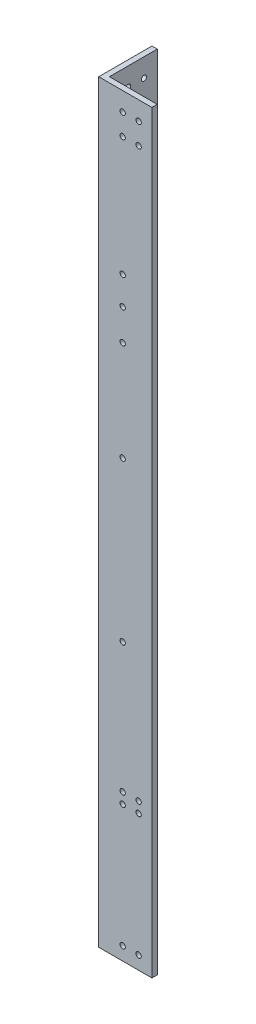
SolidWorks part; units mm, degrees
ref_plane "Front Plane" through (0, 0, 0) normal (0, 0, 1) x (1, 0, 0)
ref_plane "Top Plane" through (0, 0, 0) normal (0, 1, 0) x (1, 0, 0)
ref_plane "Right Plane" through (0, 0, 0) normal (1, 0, 0) x (0, 0, -1)
sketch "Sketch2" plane through (0, 0, 0) normal (0, 1, 0) x (1, 0, 0)
  line L0 (0, 31.75) -> (3.175, 31.75)
  line L1 (3.175, 31.75) -> (3.175, 3.175)
  line L2 (3.175, 3.175) -> (31.75, 3.175)
  line L3 (31.75, 3.175) -> (31.75, 0)
  line L4 (31.75, 0) -> (0, 0)
  line L5 (0, 0) -> (0, 31.75)
  point P9 (1.5875, 31.75)
  point P10 (31.75, 1.5875)
  dimension "D4" = 3.175
  dimension "D1" = 31.75
  dimension "D2" = 31.75
  dimension "D3" = 3.175
extrude "Boss-Extrude1" add sketch "Sketch2" along normal blind 450
sketch "FrontSideHoles-Sketch3" plane through (0, 0, 0) normal (0, 0, 1) x (1, 0, 0)
  line L0 (0, 0) -> (31.75, 0) construction
  line L3 (0, 450) -> (0, 0) construction
  circle A0 centre (14.2875, 81.1125) radius 1.5875
  circle A1 centre (23.8125, 81.1125) radius 1.5875
  circle A2 centre (14.2875, 87.4625) radius 1.5875
  circle A3 centre (23.8125, 87.4625) radius 1.5875
  circle A4 centre (14.2875, 438.8875) radius 1.5875
  circle A5 centre (14.2875, 426.1875) radius 1.5875
  circle A6 centre (23.8125, 438.8875) radius 1.5875
  circle A7 centre (23.8125, 426.1875) radius 1.5875
  circle A8 centre (14.2875, 338.1776) radius 1.5875
  circle A9 centre (14.2875, 319.6526) radius 1.5875
  circle A10 centre (14.2875, 260) radius 1.5875
  circle A11 centre (14.2875, 165) radius 1.5875
  circle A12 centre (14.2875, 355) radius 1.5875
  circle A13 centre (14.2875, 7.9375) radius 1.5875
  circle A14 centre (23.8125, 7.9375) radius 1.5875
  dimension "D4" = 3.175
  dimension "D1" = 81.1125
  dimension "D2" = 14.2875
  dimension "D8" = 11.1125
  dimension "D11" = 18.525
  dimension "D5" = 6.35
  dimension "D3" = 9.525
  dimension "D7" = 12.7
  dimension "D9" = 319.6526
  dimension "D6" = 165
  dimension "D10" = 95
  dimension "D13" = 95
  dimension "D12" = 7.9375
sketch "LeftSideHoles-Sketch4" plane through (0, 0, 0) normal (-1, 0, 0) x (0, 0, 1)
  line L0 (-31.75, 450) -> (0, 450) construction
  line L1 (0, 450) -> (0, 0) construction
  line L3 (-31.75, 0) -> (0, 0) construction
  circle A0 centre (-23.8125, 81.1125) radius 1.5875
  circle A1 centre (-14.2875, 81.1125) radius 1.5875
  circle A2 centre (-23.8125, 87.4625) radius 1.5875
  circle A3 centre (-14.2875, 87.4625) radius 1.5875
  circle A4 centre (-23.8125, 438.8875) radius 1.5875
  circle A5 centre (-14.2875, 438.8875) radius 1.5875
  circle A6 centre (-23.8125, 426.1875) radius 1.5875
  circle A7 centre (-14.2875, 426.1875) radius 1.5875
  circle A8 centre (-23.8125, 332.6026) radius 1.5875
  circle A9 centre (-14.2875, 332.6026) radius 1.5875
  circle A10 centre (-23.8125, 319.9026) radius 1.5875
  circle A11 centre (-14.2875, 319.9026) radius 1.5875
  circle A12 centre (-23.8125, 7.9375) radius 1.5875
  circle A13 centre (-14.2875, 7.9375) radius 1.5875
  circle A14 centre (-14.2875, 165) radius 1.5875
  circle A15 centre (-14.2875, 260) radius 1.5875
  circle A16 centre (-14.2875, 355) radius 1.5875
  dimension "D4" = 3.175
  dimension "D2" = 14.2875
  dimension "D7" = 12.7
  dimension "D13" = 95
  dimension "D3" = 81.1125
  dimension "D6" = 11.1125
  dimension "D5" = 6.35
  dimension "D10" = 7.9375
  dimension "D9" = 12.7
  dimension "D11" = 9.525
  dimension "D8" = 332.6026
  dimension "D12" = 165
  dimension "D14" = 95
extrude "FrontSideHoles-Cut-Extrude1" cut sketch "FrontSideHoles-Sketch3" against normal blind 3.175
extrude "LeftSideHoles-Cut-Extrude2" cut sketch "LeftSideHoles-Sketch4" against normal blind 3.175
equation "\"RailThickness\"= .125in'Spec"
equation "\"VSWidth\"= 1.25in'Spec"
equation "\"VSHeight\"= 1.25in'Spec"
equation "\"VSLength\"= 450mm"
equation "\"HoleOffsetFromEdge\"= \"RailThickness\" * 2.5"
equation "\"HoleOffsetFromSide\"= \"RailThickness\" * 3.5"
equation "\"LegHeight\"= 70mm'Space needed for PSU/Stepper/Electronics"
equation "\"VSBottomSideRailHoleY1FromBottomOfLowerRail\"= \"V1 BottomOfLowerRail\" + \"HoleOffsetFromSide\"'Equals 70.1125"
equation "\"VSSideRailHoleX1FromSide\"= \"HoleOffsetFromSide\" + \"RailThickness\""
equation "\"FasteningHoleDiameter\"= .125in"
equation "\"VSBottomSideRailHoleY2FromY1\"= \"LowerRailHeight\" - \"HoleOffsetFromSide\" - \"HoleOffsetFromEdge\"'Equals 6.35"
equation "\"VSTopSideRailHoleY1FromEdge\"= \"HoleOffsetFromEdge\" + \"RailThickness\""
equation "\"D4@FrontSideHoles-Sketch3\" = \"FasteningHoleDiameter\""
equation "\"D1@FrontSideHoles-Sketch3\" = \"VSBottomSideRailHoleY1FromBottomOfLowerRail\""
equation "\"D2@FrontSideHoles-Sketch3\" = \"VSSideRailHoleX1FromSide\""
equation "\"D1@Boss-Extrude1\"=\"VSLength\""
equation "\"D4@LeftSideHoles-Sketch4\" = \"FasteningHoleDiameter\""
equation "\"D3@LeftSideHoles-Sketch4\"= \"VSBottomSideRailHoleY1FromBottomOfLowerRail\""
equation "\"D2@LeftSideHoles-Sketch4\" = \"VSSideRailHoleX1FromSide\""
equation "\"D8@FrontSideHoles-Sketch3\" = \"VSTopSideRailHoleY1FromEdge\""
equation "\"D6@LeftSideHoles-Sketch4\" = \"VSTopSideRailHoleY1FromEdge\""
equation "\"VSMidSideRailHoleY1FromV8TopOfMidSideRail\"= \"V8 ToTopOfMidSideRail\" - \"HoleOffsetFromEdge\"'Equals 308.2875"
equation "\"LowerRailHeight\"= 1.00in"
equation "\"D1@Sketch2\"=\"VSHeight\""
equation "\"D2@Sketch2\"=\"VSWidth\""
equation "\"TopRailHeight\"= 1.25in"
equation "\"MidSideRailHeight\"= 1.25in"
equation "\"D5@LeftSideHoles-Sketch4\"=\"VSBottomSideRailHoleY2FromY1\""
equation "\"D5@FrontSideHoles-Sketch3\"=\"VSBottomSideRailHoleY2FromY1\""
equation "\"D10@LeftSideHoles-Sketch4\"=\"HoleOffsetFromEdge\""
equation "\"VSMidSideRailHoleY2FromY1\"= \"MidSideRailHeight\" - \"HoleOffsetFromSide\" - \"HoleOffsetFromEdge\"'Equals 12.7"
equation "\"D9@LeftSideHoles-Sketch4\"=\"VSMidSideRailHoleY2FromY1\""
equation "\"VSSideRailHoleX2FromX1\"= \"VSWidth\" - \"VSSideRailHoleX1FromSide\" - \"HoleOffsetFromEdge\""
equation "\"D3@FrontSideHoles-Sketch3\"=\"VSSideRailHoleX2FromX1\""
equation "\"D7@FrontSideHoles-Sketch3\"=\"VSMidSideRailHoleY2FromY1\""
equation "\"D11@LeftSideHoles-Sketch4\"=\"VSSideRailHoleX2FromX1\""
equation "\"VSTopSideRailHoleY2FromY1\"= \"TopRailHeight\" - \"VSTopSideRailHoleY1FromEdge\" - \"HoleOffsetFromEdge\"'Equals 12.7"
equation "\"D7@LeftSideHoles-Sketch4\"=\"VSTopSideRailHoleY2FromY1\""
equation "\"BeltTensionerInnerHeight\"= \"20TGT2PulleyWidth\" * 2 + \"1mmSpacer\" * 3"
equation "\"20TGT2PulleyWidth\"= 8.7mm'The STL of the Pulley in the diagram is a bit larger"
equation "\"1mmSpacer\"= 1mm"
equation "\"BeltTensionerHeight\"= \"BeltTensionerInnerHeight\" + \"BeltTensionerUpperLowerWallThickness\" * 2"
equation "\"BeltTensionerUpperLowerWallThickness\"= 7mm"
equation "\"D11@FrontSideHoles-Sketch3\"=\"VSBeltTensionerHoleY2FromY1\""
equation "\"VSBeltTensionerHoleY1FromBottom\"= \"V9 FromBottomGantryPulleyToBottomOfBeltTensioner\" + \"HoleOffsetFromEdge\""
equation "\"VSBeltTensionerHoleY2FromY1\"= \"BeltTensionerHeight\" - \"HoleOffsetFromEdge\" * 2"
equation "\"V1 BottomOfLowerRail\"= \"LegHeight\""
equation "\"StepperShaftLength\"= 24mm'Pulley will be attached to the end"
equation "\"ZAxisLeadScrewLength\"= 200mm"
equation "\"LM8UUHeight\"= 24mm'Spec"
equation "\"V2 ToBedAtTopOfZAxis\"= \"V1 BottomOfLowerRail\" + \"StepperShaftLength\" + \"ZAxisLeadScrewLength\" - \"LM8UUHeight\" / 2"
equation "\"HotEndToTopOfXAxisGB\"= 63.315144mm'Measured from the100.Should be 63.315144"
equation "\"TopOfGBToBottomOfLinearRail\"= \"LinearGBWidth\" / 2 + \"LinearRailWidth\" / 2"
equation "\"LinearGBWidth\"= 27mm'Spec"
equation "\"V5 ToBottomOfXAxisLinearRail\"= \"V4 ToTopOfBuildPlate/HotEndTip\" + \"HotEndToTopOfXAxisGB\" - \"TopOfGBToBottomOfLinearRail\""
equation "\"LinearRailWidth\"= 12mm'Spec"
equation "\"V6 ToBottomOfGantryPulley\"= \"V5 ToBottomOfXAxisLinearRail\" - \"DistanceFromGABTopToLowerPulley\""
equation "\"GABUpperHeight\"= 6mm"
equation "\"GABMidWallHeight\"= 28mm'Must equal 28 or changes alignment"
equation "\"GABMidShortRiserHeight\"= \"GABMidWallHeight\" / 2 - \"20TGT2PulleyWidth\"'Equals 5.3"
equation "\"GABRiserBossOffset\"= 0.8mm'Aligns Pulleys"
equation "\"DistanceFromGABTopToLowerPulley\"= \"GABUpperHeight\" + \"GABMidWallHeight\" - \"GABMidShortRiserHeight\" + \"GABRiserBossOffset\" / 2"
equation "\"V7 ToTopOfMidBackRail\"= \"V6 ToBottomOfGantryPulley\" + \"StepperShaftLength\""
equation "\"D8@LeftSideHoles-Sketch4\"= \"VSMidSideRailHoleY1FromV8TopOfMidSideRail\""
equation "\"BedToBuildPlateStandoffLength\"= 15mm"
equation "\"BuildPlateHeight\"= 8mm'Spec"
equation "\"V4 ToTopOfBuildPlate/HotEndTip\"= \"V2 ToBedAtTopOfZAxis\" + \"BedToBuildPlateStandoffLength\" + \"BuildPlateHeight\""
equation "\"D9@FrontSideHoles-Sketch3\"=\"VSBeltTensionerHoleY1FromBottom\""
equation "\"V8 ToTopOfMidSideRail\"= \"V7 ToTopOfMidBackRail\" - \"RailThickness\""
equation "\"V9 FromBottomGantryPulleyToBottomOfBeltTensioner\"= \"V6 ToBottomOfGantryPulley\" - \"BeltTensionerUpperLowerWallThickness\" - \"1mmSpacer\""
equation "\"BeltTensionerMountingHoleOffsetFromEdge\"= \"HoleOffsetFromEdge\""
equation "\"VSBeltTensionerXMountingHoleOffsetFromSide\"= \"BeltTensionerMountingHoleOffsetFromEdge\" + \"RailThickness\" * 2"
equation "\"VSEnclosureOffsets\"= ( \"VSLength\" - \"LegHeight\" ) / 4"
equation "\"D6@FrontSideHoles-Sketch3\"=\"LegHeight\" + \"VSEnclosureOffsets\""
equation "\"D10@FrontSideHoles-Sketch3\"=\"VSEnclosureOffsets\""
equation "\"D13@FrontSideHoles-Sketch3\"=\"VSEnclosureOffsets\""
equation "\"D12@FrontSideHoles-Sketch3\"=\"HoleOffsetFromEdge\""
equation "\"D13@LeftSideHoles-Sketch4\"=\"VSEnclosureOffsets\""
equation "\"D14@LeftSideHoles-Sketch4\"=\"VSEnclosureOffsets\""
equation "\"D12@LeftSideHoles-Sketch4\"=\"LegHeight\" + \"VSEnclosureOffsets\""
